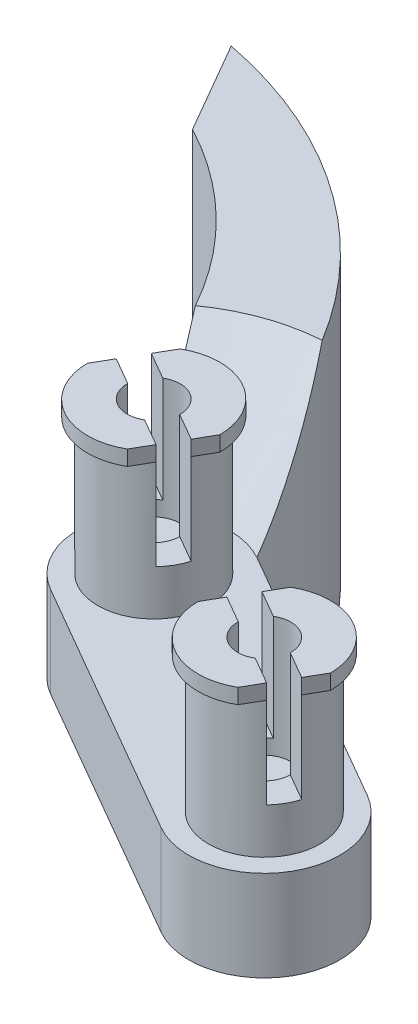
SolidWorks part; units mm, degrees
ref_plane "Front Plane" through (0, 0, 0) normal (0, 0, 1) x (1, 0, 0)
ref_plane "Top Plane" through (0, 0, 0) normal (0, 1, 0) x (1, 0, 0)
ref_plane "Right Plane" through (0, 0, 0) normal (1, 0, 0) x (0, 0, -1)
sketch "Sketch1" plane through (0, 0, 0) normal (0, 1, 0) x (1, 0, 0)
  line L0 (-19.8205, 5.6699) -> (-2.5, -4.3301)
  line L1 (2.5, 4.3301) -> (-14.8205, 14.3301)
  line L2 (-17.3205, 15) -> (-43, 15) construction
  line L3 (-43, 15) -> (-50, 15) construction
  line L4 (0, 0) -> (-21.6506, 12.5) construction
  line L5 (-19.8205, 5.6699) -> (-14.8205, 14.3301) construction
  line L6 (0, -5) -> (-15.3949, -5) construction
  line L7 (0, 0) -> (2.5, 4.3301) construction
  line L8 (-21.6506, 7.5) -> (-34.4904, 29.7391) construction
  line L9 (-34.4904, 29.7391) -> (-37.9904, 35.8013)
  circle A0 centre (0, 0) radius 3.7
  circle A1 centre (0, 0) radius 5
  arc A2 (-43, 15) -> (-21.6506, 12.5) centre (-29.7001, 36.1687) ccw construction
  arc A3 (-14.8205, 14.3301) -> (-14.9376, 14.3957) centre (-7.2881, 27.928) cw
  circle A4 centre (0, 0) radius 1.75
  circle A5 centre (-17.3205, 10) radius 5
  circle A6 centre (-17.3205, 10) radius 3.7
  circle A7 centre (-17.3205, 10) radius 1.75
  arc A8 (-50, 15) -> (-19.8205, 5.6699) centre (-27.3769, 34.7026) ccw construction
  arc A9 (-37.9904, 35.8013) -> (-14.8205, 14.3301) centre (-43.7418, 6.3577) cw
  arc A10 (-34.4904, 29.7391) -> (-21.6506, 12.5) centre (-46.173, 7.6367) cw
  arc A11 (-21.6506, 12.5) -> (-14.8205, 14.3301) centre (-17.2875, 9.8767) cw
  dimension "D1" = 7.4
  dimension "D7" = 3.5
  dimension "D8" = 30
  dimension "D6" = 25
  dimension "D4" = 7
  dimension "D5" = 50
  dimension "D10" = 30
  dimension "D9" = 10
extrude "Boss-Extrude4" add sketch "Sketch1" along normal blind 6 contours A0 A4 | A4 | A1 A0 | A5 L0 A1 L1 | A3 A5 A6 | A6 A7 | A7 region at (-8.6603, 0, -5) region at (-22.0138, 0, -8.7424) region at (-4.2077, 0, -2.4293) region at (-3.5953, 0, 0) region at (0, 0, 0) region at (-20.9159, 0, -10) region at (-17.3205, 0, -10)
extrude "Boss-Extrude6" add sketch "Sketch1<10>" along normal blind 15 contours A7 | A6 | A0 | A4 region at (-17.3205, 0, -10)
sketch "Sketch1<10>" plane through (0, 0, 0) normal (0, 1, 0) x (1, 0, 0) same geometry as "Sketch1"
sketch "Sketch5" plane through (0, 15, 0) normal (0, 1, 0) x (1, 0, 0)
  line L0 (-5.8014, 9.9517) -> (-10.8014, 1.2915) construction
  line L3 (4.3301, -2.5) -> (-21.6506, 12.5) construction
  line L4 (-20.0141, 12.5366) -> (-18.2203, 11.501)
  line L5 (-19.1705, 6.7957) -> (-15.4705, 13.2043) construction
  line L6 (-13.7769, 8.9356) -> (-15.5707, 9.9713)
  line L7 (-14.6269, 7.4634) -> (-16.4207, 8.499)
  line L8 (-20.8641, 11.0644) -> (-19.0703, 10.0287)
  line L9 (-1.85, -3.2043) -> (1.85, 3.2043) construction
  line L10 (2.6936, -2.5366) -> (0.8998, -1.501)
  line L11 (-3.5436, 1.0644) -> (-1.7498, 0.0287)
  line L12 (-2.6936, 2.5366) -> (-0.8998, 1.501)
  line L13 (3.5436, -1.0644) -> (1.7498, -0.0287)
  circle A3 centre (-17.3205, 10) radius 1.75 construction
  circle A4 centre (0, 0) radius 1.75 construction
  circle A5 centre (-17.3205, 10) radius 1.75 construction
  arc A7 (-20.8641, 11.0644) -> (-20.0141, 12.5366) centre (-17.3205, 10) cw
  arc A8 (-19.0703, 10.0287) -> (-18.2203, 11.501) centre (-17.3205, 10) cw
  arc A9 (-16.4207, 8.499) -> (-15.5707, 9.9713) centre (-17.3205, 10) ccw
  arc A10 (-14.6269, 7.4634) -> (-13.7769, 8.9356) centre (-17.3205, 10) ccw
  circle A11 centre (0, 0) radius 1.75 construction
  arc A12 (-3.5436, 1.0644) -> (-2.6936, 2.5366) centre (0, 0) cw
  arc A13 (-1.7498, 0.0287) -> (-0.8998, 1.501) centre (0, 0) cw
  arc A14 (0.8998, -1.501) -> (1.7498, -0.0287) centre (0, 0) ccw
  arc A15 (2.6936, -2.5366) -> (3.5436, -1.0644) centre (0, 0) ccw
  dimension "D1" = 0.85
extrude "Cut-Extrude1" cut sketch "Sketch5" against normal blind 6
sketch "Sketch6" plane through (0, 6, 0) normal (0, 1, 0) x (1, 0, 0)
  line L0 (-10.2328, 2.2762) -> (-5.2328, 10.9365) construction
  circle A0 centre (-17.3205, 10) radius 1.75
  circle A1 centre (0, 0) radius 1.75
extrude "Boss-Extrude7" add sketch "Sketch6" along normal blind 2
sketch "Sketch8" plane through (0, 15, 0) normal (0, 1, 0) x (1, 0, 0)
  line L0 (-19.8205, 5.6699) -> (-14.8205, 14.3301) construction
  line L1 (-18.2203, 11.501) -> (-20.4471, 12.7866)
  line L2 (-18.2203, 11.501) -> (-20.0141, 12.5366) construction
  line L3 (-17.3205, 10) -> (-14.1162, 8.15) construction
  line L4 (0, 0) -> (-21.6506, 12.5) construction
  line L5 (-17.3205, 10) -> (-15.4705, 13.2043) construction
  line L6 (-15.5707, 9.9713) -> (-13.3439, 8.6856)
  line L7 (-16.4207, 8.499) -> (-14.1939, 7.2134)
  line L8 (-19.0703, 10.0287) -> (-21.2971, 11.3144)
  line L9 (-11.1603, 0.6699) -> (-6.1603, 9.3301) construction
  line L10 (-19.8205, 5.6699) -> (-2.5, -4.3301) construction
  line L11 (2.5, 4.3301) -> (-14.8205, 14.3301) construction
  line L12 (0, 0) -> (1.85, 3.2043) construction
  line L13 (0, 0) -> (-3.2043, 1.85) construction
  line L14 (0.8998, -1.501) -> (3.1266, -2.7866)
  line L15 (-1.7498, 0.0287) -> (-3.9766, 1.3144)
  line L16 (-0.8998, 1.501) -> (-3.1266, 2.7866)
  line L17 (1.7498, -0.0287) -> (3.9766, -1.3144)
  arc A0 (-19.0703, 10.0287) -> (-16.4207, 8.499) centre (-17.3205, 10) ccw
  circle A2 centre (-17.3205, 10) radius 3.7 construction
  arc A3 (-15.5707, 9.9713) -> (-18.2203, 11.501) centre (-17.3205, 10) ccw
  arc A4 (-21.2971, 11.3144) -> (-14.1939, 7.2134) centre (-17.4005, 9.8614) ccw
  arc A5 (-20.4471, 12.7866) -> (-13.3439, 8.6856) centre (-17.2405, 10.1386) cw
  arc A6 (3.9766, -1.3144) -> (-3.1266, 2.7866) centre (0.08, 0.1386) ccw
  arc A7 (3.1266, -2.7866) -> (-3.9766, 1.3144) centre (-0.08, -0.1386) cw
  arc A8 (-0.8998, 1.501) -> (1.7498, -0.0287) centre (0, 0) cw
  arc A9 (0.8998, -1.501) -> (-1.7498, 0.0287) centre (0, 0) cw
  dimension "D2" = 0.16
  dimension "D1" = 0.5
extrude "Boss-Extrude8" add sketch "Sketch8" along normal blind 1
extrude "Boss-Extrude10" add sketch "Sketch1<12>" along normal blind 13 and the other way blind 6 contours A9 L9 A10 A11
sketch "Sketch1<12>" plane through (0, 0, 0) normal (0, 1, 0) x (1, 0, 0) same geometry as "Sketch1"
chamfer "Chamfer2" distance 7 angle 45 2 edges at (-18.6051, -6, -14.7943) (-18.6051, 13, -14.7943)
sketch "Sketch9" plane through (0, 16, 0) normal (0, 1, 0) x (1, 0, 0)
  line L0 (-18.1955, 8.4845) -> (-16.4455, 11.5155) construction
  line L1 (-20.8641, 11.0644) -> (-21.5592, 9.8605)
  line L2 (-20.0141, 12.5366) -> (-19.319, 13.7406)
  line L3 (-21.5592, 9.8605) -> (-22.1015, 10.1736)
  line L4 (-22.1015, 10.1736) -> (-21.4064, 11.3775)
  line L5 (-21.4064, 11.3775) -> (-20.8641, 11.0644)
  line L6 (-20.0141, 12.5366) -> (-20.6054, 12.878)
  line L7 (-20.6054, 12.878) -> (-19.9103, 14.0819)
  line L8 (-19.9103, 14.0819) -> (-19.319, 13.7406)
  line L9 (-20.4471, 12.7866) -> (-18.2203, 11.501) construction
  line L10 (-20.8641, 11.0644) -> (-19.0703, 10.0287) construction
  line L11 (-11.1603, 0.6699) -> (-6.1603, 9.3301) construction
  line L12 (-19.8205, 5.6699) -> (-2.5, -4.3301) construction
  line L13 (2.5, 4.3301) -> (-14.8205, 14.3301) construction
  line L14 (-12.4905, 9.7982) -> (-13.0818, 10.1395)
  line L15 (-13.1856, 8.5942) -> (-12.4905, 9.7982)
  line L16 (-13.7769, 8.9356) -> (-13.1856, 8.5942)
  line L17 (-14.0846, 7.1502) -> (-14.6269, 7.4634)
  line L18 (-14.7797, 5.9463) -> (-14.0846, 7.1502)
  line L19 (-15.322, 6.2594) -> (-14.7797, 5.9463)
  line L20 (-13.7769, 8.9356) -> (-13.0818, 10.1395)
  line L21 (-14.6269, 7.4634) -> (-15.322, 6.2594)
  line L22 (-3.5436, 1.0644) -> (-4.2387, -0.1395)
  line L23 (-4.2387, -0.1395) -> (-4.781, 0.1736)
  line L24 (-4.781, 0.1736) -> (-4.0859, 1.3775)
  line L25 (-0.875, -1.5155) -> (0.875, 1.5155) construction
  line L26 (-2.6936, 2.5366) -> (-1.9985, 3.7406)
  line L27 (-4.0859, 1.3775) -> (-3.5436, 1.0644)
  line L28 (-2.6936, 2.5366) -> (-3.2849, 2.878)
  line L29 (-3.2849, 2.878) -> (-2.5898, 4.0819)
  line L30 (-2.5898, 4.0819) -> (-1.9985, 3.7406)
  line L31 (4.83, -0.2018) -> (4.2387, 0.1395)
  line L32 (4.1349, -1.4058) -> (4.83, -0.2018)
  line L33 (3.5436, -1.0644) -> (4.1349, -1.4058)
  line L34 (3.2359, -2.8498) -> (2.6936, -2.5366)
  line L35 (2.5408, -4.0537) -> (3.2359, -2.8498)
  line L36 (1.9985, -3.7406) -> (2.5408, -4.0537)
  line L37 (3.5436, -1.0644) -> (4.2387, 0.1395)
  line L38 (2.6936, -2.5366) -> (1.9985, -3.7406)
  arc A0 (-19.0703, 10.0287) -> (-16.4207, 8.499) centre (-17.3205, 10) ccw construction
  arc A1 (-15.5707, 9.9713) -> (-18.2203, 11.501) centre (-17.3205, 10) ccw construction
  arc A2 (-21.2971, 11.3144) -> (-14.1939, 7.2134) centre (-17.4005, 9.8614) ccw construction
  arc A3 (-13.3439, 8.6856) -> (-20.4471, 12.7866) centre (-17.2405, 10.1386) ccw construction
extrude "Cut-Extrude2" cut sketch "Sketch9" against normal up to surface (1 mm away) up to face at (-18.5353, 15, -7.8958)
